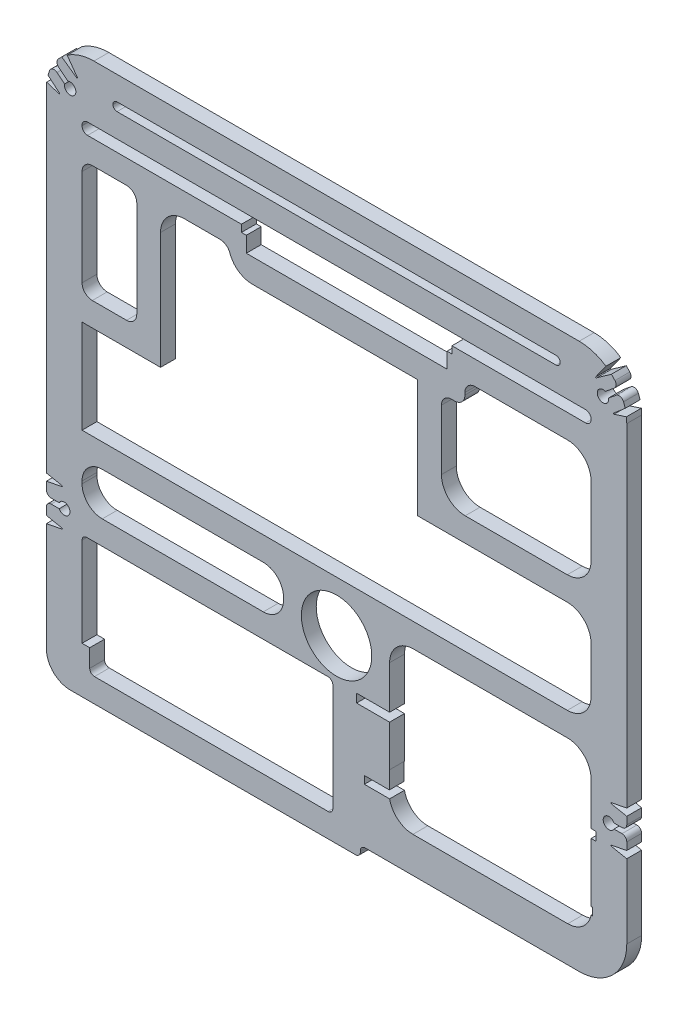
SolidWorks part; units mm, degrees
ref_plane "Front Plane" through (0, 0, 0) normal (0, 0, 1) x (1, 0, 0)
ref_plane "Top Plane" through (0, 0, 0) normal (0, 1, 0) x (1, 0, 0)
ref_plane "Right Plane" through (0, 0, 0) normal (1, 0, 0) x (0, 0, -1)
sketch "Sketch1" plane through (0, 0, 0) normal (0, 0, 1) x (1, 0, 0)
  line L0 (63.9883, 61.406) -> (63.9883, 57.596) construction
  line L1 (11.1776, 3.1158) -> (73.1542, 3.1158)
  line L2 (11.1776, 3.1158) -> (11.1776, 61.406)
  line L3 (11.1776, 61.406) -> (73.1542, 61.406)
  line L4 (73.1542, 3.1158) -> (73.1542, 61.406)
  line L5 (69.3442, 57.596) -> (14.9876, 57.596)
  line L6 (69.3442, 57.596) -> (69.3442, 6.9258)
  line L7 (69.3442, 6.9258) -> (14.9876, 6.9258)
  line L8 (14.9876, 57.596) -> (14.9876, 6.9258)
  line L9 (63.9883, 59.501) -> (18.0707, 59.501) construction
  line L10 (14.9876, 39.3805) -> (11.1776, 39.3805) construction
  line L11 (13.0826, 39.3805) -> (13.0826, 23.9527) construction
  line L12 (13.5248, 6.9258) -> (13.5248, 3.1158) construction
  line L13 (13.5248, 5.0208) -> (21.1598, 5.0208) construction
  line L14 (73.1542, 38.1916) -> (69.3442, 38.1916) construction
  line L15 (71.2492, 38.1916) -> (71.2492, 22.3321) construction
  line L16 (55.7422, 59.501) -> (30.5962, 59.501) construction
  line L19 (42.3087, 5.0208) -> (41.7626, 5.0208) construction
  line L21 (69.3442, 23.8281) -> (69.3442, 52.516) construction
  line L22 (14.9876, 47.563) -> (14.9876, 23.8281) construction
  dimension "D1" = 3.81
  dimension "D2" = 3.81
extrude "Boss-Extrude1" add sketch "Sketch1" along normal blind 1.5875
sketch "Sketch2" plane through (0, 0, 0) normal (0, 0, -1) x (-1, 0, 0)
  line L0 (-69.3442, 6.9258) -> (-69.3442, 57.596) construction
  line L1 (-69.3442, 26.6348) -> (-14.9876, 26.6348)
  line L2 (-69.3442, 26.6348) -> (-69.3442, 24.0948)
  line L3 (-69.3442, 24.0948) -> (-14.9876, 24.0948)
  line L4 (-14.9876, 26.6348) -> (-14.9876, 24.0948)
  line L5 (-14.9876, 57.596) -> (-14.9876, 6.9258) construction
  line L6 (-20.1206, 26.6348) -> (-57.8206, 26.6348) construction
  line L7 (-53.9642, 53.4304) -> (-53.9642, 51.7667)
  line L8 (-32.5266, 53.4304) -> (-32.0059, 53.4304)
  line L9 (-32.5266, 51.7667) -> (-53.9642, 51.7667) construction
  line L10 (-32.5266, 51.7667) -> (-32.5266, 53.4304) construction
  line L11 (-69.3442, 54.1924) -> (-54.4849, 54.1924)
  line L12 (-69.3442, 54.1924) -> (-69.3442, 51.6524)
  line L13 (-69.3442, 51.6524) -> (-55.8692, 51.6524)
  line L14 (-14.9876, 54.1924) -> (-14.9876, 51.6524)
  line L15 (-69.3442, 57.596) -> (-14.9876, 57.596)
  line L16 (-69.3442, 57.596) -> (-69.3442, 55.4243)
  line L17 (-69.3442, 55.4243) -> (-14.9876, 55.4243)
  line L18 (-14.9876, 57.596) -> (-14.9876, 55.4243)
  line L19 (-69.3442, 57.596) -> (-14.9876, 57.596) construction
  line L20 (-54.4849, 54.1924) -> (-54.4849, 53.4304)
  line L21 (-62.3462, 55.4243) -> (-23.9922, 55.4243) construction
  line L22 (-54.4849, 53.4304) -> (-53.9642, 53.4304)
  line L23 (-32.5266, 51.7667) -> (-53.9642, 51.7667)
  line L24 (-32.5266, 51.7667) -> (-32.5266, 53.4304)
  line L25 (-55.8692, 51.6524) -> (-55.8692, 49.2267)
  line L26 (-55.8692, 49.2267) -> (-30.6216, 49.2267)
  line L27 (-30.6216, 49.2267) -> (-30.6216, 51.6524)
  line L28 (-30.6216, 51.6524) -> (-14.9876, 51.6524)
  line L29 (-32.0059, 53.4304) -> (-32.0059, 54.1924)
  line L30 (-62.3462, 54.1924) -> (-23.9922, 54.1924) construction
  line L32 (-54.4849, 53.4304) -> (-54.4849, 54.1924) construction
  line L33 (-32.0059, 53.4304) -> (-54.4849, 53.4304) construction
  line L34 (-32.0059, 54.1924) -> (-14.9876, 54.1924)
  line L36 (-32.0059, 53.4304) -> (-32.0059, 54.1924) construction
  line L37 (-32.5266, 51.7667) -> (-32.5266, 53.4304) construction
  dimension "D1" = 2.54
  dimension "D2" = 1.905
  dimension "D3" = 2.54
  dimension "D4" = 1.905
  dimension "D5" = 2.54
extrude "Boss-Extrude2" add sketch "Sketch2" against normal up to surface (1.5875 mm away) up to face at (42.1659, 32.2609, 1.5875)
sketch "Sketch3" plane through (0, 0, 0) normal (0, 0, -1) x (-1, 0, 0)
  line L0 (-57.8206, 36.6348) -> (-50.8206, 36.6348) construction
  line L1 (-57.8206, 36.6348) -> (-50.8206, 36.6348)
  line L2 (-57.8206, 36.6348) -> (-69.3442, 36.6348)
  line L3 (-69.3442, 26.6348) -> (-69.3442, 51.6524) construction
  line L4 (-69.3442, 36.6348) -> (-69.3442, 39.1748)
  line L5 (-69.3442, 39.1748) -> (-53.3606, 39.1748)
  line L6 (-50.8206, 28.408) -> (-50.8206, 36.6348)
  line L7 (-50.8206, 28.408) -> (-50.8206, 49.2267)
  line L8 (-55.8692, 49.2267) -> (-30.6216, 49.2267) construction
  line L9 (-50.8206, 49.2267) -> (-53.3606, 49.2267)
  line L10 (-53.3606, 49.2267) -> (-53.3606, 39.1748)
  line L11 (-23.3706, 36.6348) -> (-20.1206, 36.6348) construction
  line L12 (-23.3706, 36.6348) -> (-20.1206, 36.6348)
  line L13 (-20.1206, 36.6348) -> (-14.9876, 36.6348)
  line L14 (-14.9876, 51.6524) -> (-14.9876, 26.6348) construction
  line L15 (-14.9876, 36.6348) -> (-14.9876, 39.1748)
  line L16 (-14.9876, 39.1748) -> (-20.8306, 39.1748)
  line L17 (-20.8306, 39.1748) -> (-20.8306, 51.6524)
  line L18 (-30.6216, 51.6524) -> (-14.9876, 51.6524) construction
  line L19 (-20.8306, 51.6524) -> (-23.3706, 51.6524)
  line L20 (-23.3706, 51.6524) -> (-23.3706, 36.6348)
  line L21 (-23.3706, 36.6348) -> (-16.2412, 25.8471)
  line M22 (-69.3442, 26.6348) -> (-69.3442, 51.6524)
  line M25 (-55.8692, 49.2267) -> (-30.6216, 49.2267)
  line M27 (-30.6216, 51.6524) -> (-14.9876, 51.6524)
  line M28 (-14.9876, 51.6524) -> (-14.9876, 26.6348)
  dimension "D1" = 2.54
  dimension "D2" = 2.54
  dimension "D3" = 2.54
  dimension "D4" = 2.54
extrude "Boss-Extrude3" add sketch "Sketch3" against normal up to surface (1.5875 mm away) contours L10 L5 L2 L1 L6 L7 M25 M22 | L20 L12 L13 L16 L17 M27 M28 region at (63.5824, 36.8588, 0) region at (20.9265, 42.3962, 0) up to face at (42.8855, 53.7395, 1.5875)
sketch "Sketch4" plane through (0, 0, 0) normal (0, 0, -1) x (-1, 0, 0)
  line L0 (-69.3442, 24.0948) -> (-14.9876, 24.0948) construction
  line L1 (-47.8301, 24.0948) -> (-36.5017, 24.0948)
  line L2 (-47.8301, 24.0948) -> (-47.8301, 6.9258)
  line L3 (-47.8301, 6.9258) -> (-36.5017, 6.9258)
  line L4 (-36.5017, 24.0948) -> (-36.5017, 6.9258)
  line L5 (-14.9876, 6.9258) -> (-69.3442, 6.9258) construction
  line L6 (-45.9251, 21.2246) -> (-47.8301, 21.2246) construction
  line L7 (-38.4067, 21.2246) -> (-36.5017, 21.2246) construction
  circle A0 centre (-42.1659, 21.2246) radius 3.7592 construction
  dimension "D1" = 1.905
extrude "Boss-Extrude4" add sketch "Sketch4" against normal up to surface (1.5875 mm away) up to face at (17.9091, 45.4136, 1.5875)
sketch "Sketch5" plane through (0, 0, 0) normal (0, 0, -1) x (-1, 0, 0)
  line L0 (-15.8038, 16.9715) -> (-41.7626, 16.9715) construction
  line L3 (-41.7626, 4.5128) -> (-41.7626, 16.9715) construction
  line L4 (-15.8038, 4.5128) -> (-41.7626, 4.5128) construction
  line L5 (-15.8038, 4.5128) -> (-15.8038, 16.9715) construction
  line L6 (-15.8038, 16.9715) -> (-41.7626, 16.9715)
  line L7 (-41.7626, 4.5128) -> (-41.7626, 16.9715)
  line L8 (-15.8038, 4.5128) -> (-41.7626, 4.5128)
  line L9 (-15.8038, 4.5128) -> (-15.8038, 16.9715)
  circle A0 centre (-42.1659, 21.2246) radius 3.7592 construction
  circle A1 centre (-42.1659, 21.2246) radius 3.7592
extrude "Cut-Extrude1" cut sketch "Sketch5" against normal up to surface (1.5875 mm away) up to face at (58.5871, 15.5103, 1.5875)
sketch "Sketch8" plane through (0, 0, 0) normal (0, 0, -1) x (-1, 0, 0)
  line L1 (-36.5017, 16.9715) -> (-14.9876, 16.9715)
  line L2 (-36.5017, 16.9715) -> (-36.5017, 19.5115)
  line L3 (-36.5017, 19.5115) -> (-14.9876, 19.5115)
  line L4 (-14.9876, 16.9715) -> (-14.9876, 19.5115)
  line L5 (-14.9876, 24.0948) -> (-14.9876, 6.9258) construction
  dimension "D1" = 2.54
extrude "Boss-Extrude5" add sketch "Sketch8" against normal up to surface (1.5875 mm away) up to face at (38.4067, 21.2246, 1.5875)
fillet "Fillet1" radius 5.08 3 edges at (73.1542, 3.1158, 0.7937) (11.1776, 61.406, 0.7937) (73.1542, 61.406, 0.7937)
fillet "Fillet2" radius 2.54 7 edges at (23.3706, 51.6524, 0.7937) (30.6216, 49.2267, 0.7937) (69.3442, 51.6524, 0.7937) (53.3606, 39.1748, 0.7937) (69.3442, 26.6348, 0.7937) (69.3442, 39.1748, 0.7937) (69.3442, 36.6348, 0.7937)
fillet "Fillet3" radius 1.0922 8 edges at (53.3606, 49.2267, 0.7937) (55.8692, 49.2267, 0.7937) (55.8692, 51.6524, 0.7937) (14.9876, 39.1748, 0.7937) (20.8306, 39.1748, 0.7937) (14.9876, 51.6524, 0.7937) (20.8306, 51.6524, 0.7937) (30.6216, 51.6524, 0.7937)
fillet "Fillet4" radius 0.5842 4 edges at (14.9876, 55.4243, 0.7937) (69.3442, 55.4243, 0.7937) (69.3442, 54.1924, 0.7937) (14.9876, 54.1924, 0.7937)
fillet "Fillet8" radius 2.159 4 edges at (36.5017, 19.5115, 0.7937) (36.5017, 24.0948, 0.7937) (14.9876, 24.0948, 0.7938) (14.9876, 19.5115, 0.7937)
sketch "Sketch6" plane through (0, 0, 0) normal (0, 0, -1) x (-1, 0, 0)
  line L0 (-16.6206, 28.1348) -> (-18.1206, 26.6348) construction
  line L1 (-18.1206, 36.6348) -> (-16.6206, 35.1348) construction
  line L2 (-16.6206, 35.1348) -> (-16.6206, 28.1348) construction
  line L3 (-16.6206, 28.1348) -> (-18.1206, 26.6348)
  line L4 (-18.1206, 36.6348) -> (-16.6206, 35.1348)
  line L5 (-16.6206, 35.1348) -> (-16.6206, 28.1348)
  line L6 (-18.1206, 36.6348) -> (-18.1206, 26.6348)
  circle A0 centre (-71.2492, 18.4306) radius 0.6096 construction
  circle A1 centre (-71.2492, 18.4306) radius 0.6096
  circle A4 centre (-70.6142, 57.596) radius 0.6096 construction
  circle A5 centre (-70.6142, 57.596) radius 0.6096
  circle A6 centre (-13.0826, 18.4306) radius 0.6096 construction
  circle A7 centre (-13.0826, 18.4306) radius 0.6096
  circle A10 centre (-13.7176, 57.596) radius 0.6096 construction
  circle A11 centre (-13.7176, 57.596) radius 0.6096
extrude "Cut-Extrude2" cut sketch "Sketch6" against normal up to surface (1.5875 mm away) up to face at (24.1846, 9.4701, 1.5875)
sketch "Sketch7" plane through (0, 0, 0) normal (0, 0, -1) x (-1, 0, 0)
  line L0 (-44.3026, 16.9715) -> (-69.8804, 16.9715) construction
  line L1 (-69.8804, 16.9715) -> (-69.8804, 16.0571) construction
  line L2 (-69.8804, 16.0571) -> (-44.3026, 16.0571) construction
  line L3 (-44.3026, 16.0571) -> (-44.3026, 16.9715) construction
  line L4 (-45.1366, 9.7751) -> (-69.5206, 9.7751) construction
  line L5 (-69.5206, 9.7751) -> (-69.5206, 8.9623) construction
  line L6 (-69.5206, 8.9623) -> (-45.1366, 8.9623) construction
  line L7 (-45.1366, 8.9623) -> (-45.1366, 9.7751) construction
  line L8 (-44.3026, 16.9715) -> (-69.8804, 16.9715)
  line L9 (-69.8804, 16.9715) -> (-69.8804, 16.0571)
  line L10 (-69.8804, 16.0571) -> (-44.3026, 16.0571)
  line L11 (-44.3026, 16.0571) -> (-44.3026, 16.9715)
  line L12 (-45.1366, 9.7751) -> (-69.5206, 9.7751)
  line L13 (-69.5206, 9.7751) -> (-69.5206, 8.9623)
  line L14 (-69.5206, 8.9623) -> (-45.1366, 8.9623)
  line L15 (-45.1366, 8.9623) -> (-45.1366, 9.7751)
  line L20 (-66.8536, 9.7751) -> (-47.8036, 9.7751)
  line L21 (-47.8036, 9.7751) -> (-47.8036, 11.6547)
  line L22 (-47.8036, 11.6547) -> (-66.8536, 11.6547)
  line L23 (-66.8536, 11.6547) -> (-66.8536, 9.7751)
  line L24 (-66.8536, 9.7751) -> (-47.8036, 9.7751)
  line L25 (-47.8036, 9.7751) -> (-47.8036, 11.6547)
  line L26 (-47.8036, 11.6547) -> (-66.8536, 11.6547)
  line L27 (-66.8536, 11.6547) -> (-66.8536, 9.7751)
  dimension "D1" = 0
extrude "Cut-Extrude3" cut sketch "Sketch7" against normal up to surface (1.5875 mm away) contours L14 L15 L12 L13 | L26 L27 L12 L25 | L10 L11 L8 L9 region at (57.0915, 16.5143, 0) region at (57.3286, 9.3687, 0) region at (57.3286, 10.7149, 0) up to face at (13.108, 57.596, 1.5875)
fillet "Fillet6" radius 0.508 4 edges at (41.7626, 16.9715, 0.7937) (41.7626, 4.5128, 0.7937) (15.8038, 4.5128, 0.7937) (14.9876, 16.9715, 0.7937)
sketch "Sketch9" plane through (0, 0, 1.5875) normal (0, 0, 1) x (1, 0, 0)
  line L0 (68.0742, 61.406) -> (16.2576, 61.406) construction
  line L1 (18.2896, 58.866) -> (66.0422, 58.866)
  line L2 (18.2896, 58.866) -> (18.2896, 57.9643)
  line L3 (18.2896, 57.9643) -> (66.0422, 57.9643)
  line L8 (66.0422, 58.866) -> (66.0422, 57.9643)
  line L9 (15.5718, 55.4243) -> (68.76, 55.4243) construction
  line L10 (11.1776, 56.326) -> (11.1776, 59.3208) construction
  line L11 (18.2896, 58.866) -> (11.1776, 58.866) construction
  line L13 (66.0422, 58.866) -> (73.1542, 58.866) construction
  line L14 (73.1542, 56.326) -> (73.1542, 56.8419) construction
  dimension "D1" = 2.54
  dimension "D2" = 2.54
  dimension "D3" = 7.112
extrude "Cut-Extrude4" cut sketch "Sketch9" against normal up to surface (1.5875 mm away) up to face at (57.106, 13.2916, 0)
fillet "Fillet7" radius 0.4318 4 edges at (18.2896, 57.9643, 0.7937) (18.2896, 58.866, 0.7937) (66.0422, 57.9643, 0.7937) (66.0422, 58.866, 0.7937)
fillet "Fillet9" radius 2.54 4 edges at (69.3442, 6.9258, 0.7937) (47.8301, 6.9258, 0.7937) (69.3442, 24.0948, 0.7937) (47.8301, 24.0948, 0.7937)
sketch "Sketch10" plane through (0, 0, 1.5875) normal (0, 0, 1) x (1, 0, 0)
  line L0 (42.1659, 24.9838) -> (42.1659, -13.4858) construction
  line L1 (11.1776, 3.1158) -> (44.7059, 3.1158)
  line L2 (11.1776, 3.1158) -> (11.1776, 1.9728)
  line L3 (11.1776, 1.9728) -> (44.7059, 1.9728)
  line L4 (44.7059, 3.1158) -> (44.7059, 1.9728)
  line L5 (16.3118, 4.5128) -> (41.2546, 4.5128) construction
  circle A0 centre (42.1659, 21.2246) radius 3.7592 construction
  dimension "D1" = 2.54
  dimension "D2" = 2.54
extrude "Boss-Extrude6" add sketch "Sketch10" against normal up to surface (1.5875 mm away) up to face at (42.1659, 58.4152, 0)
fillet "Fillet10" radius 2.54 1 edges at (11.1776, 1.9728, 0.7937)
fillet "Fillet11" radius 0.508 2 edges at (44.7059, 3.1158, 0.7937) (44.7059, 1.9728, 0.7937)
sketch "Sketch11" plane through (0, 0, 1.5875) normal (0, 0, 1) x (1, 0, 0)
  line L0 (14.486, 59.0031) -> (13.3987, 60.5253) construction
  line L1 (12.8232, 60.0693) -> (14.4151, 58.9322) construction
  line L2 (13.4744, 58.155) -> (12.501, 58.9492) construction
  line L3 (12.3178, 58.3774) -> (13.1211, 57.7221) construction
  line L4 (12.5786, 56.6017) -> (11.3522, 57.6466) construction
  line L5 (11.2145, 56.9374) -> (12.5302, 56.5147) construction
  line L6 (69.8457, 59.0031) -> (70.933, 60.5253) construction
  line L7 (71.5085, 60.0693) -> (69.9166, 58.9322) construction
  line L8 (70.8574, 58.155) -> (71.8308, 58.9492) construction
  line L9 (72.0139, 58.3774) -> (71.2106, 57.7221) construction
  line L10 (71.7531, 56.6017) -> (72.9795, 57.6466) construction
  line L11 (73.1172, 56.9374) -> (71.8016, 56.5147) construction
  line L12 (71.4982, 20.4444) -> (73.1542, 20.7756) construction
  line L13 (73.1542, 20.0136) -> (71.4982, 20.3448) construction
  line L14 (71.791, 18.71) -> (72.6462, 18.71) construction
  line L15 (72.6462, 18.1512) -> (71.791, 18.1512) construction
  line L16 (71.4982, 16.5165) -> (73.1542, 16.8477) construction
  line L17 (73.1542, 16.0857) -> (71.4982, 16.4169) construction
  line L18 (14.486, 59.0031) -> (13.3987, 60.5253)
  line L19 (12.8232, 60.0693) -> (14.4151, 58.9322)
  line L20 (13.4744, 58.155) -> (12.501, 58.9492)
  line L21 (12.3178, 58.3774) -> (13.1211, 57.7221)
  line L22 (12.5786, 56.6017) -> (11.3522, 57.6466)
  line L23 (11.2145, 56.9374) -> (12.5302, 56.5147)
  line L24 (69.8457, 59.0031) -> (70.933, 60.5253)
  line L25 (71.5085, 60.0693) -> (69.9166, 58.9322)
  line L26 (70.8574, 58.155) -> (71.8308, 58.9492)
  line L27 (72.0139, 58.3774) -> (71.2106, 57.7221)
  line L28 (71.7531, 56.6017) -> (72.9795, 57.6466)
  line L29 (73.1172, 56.9374) -> (71.8016, 56.5147)
  line L30 (71.4982, 20.4444) -> (73.1542, 20.7756)
  line L31 (73.1542, 20.0136) -> (71.4982, 20.3448)
  line L32 (71.791, 18.71) -> (72.6462, 18.71)
  line L33 (72.6462, 18.1512) -> (71.791, 18.1512)
  line L34 (71.4982, 16.5165) -> (73.1542, 16.8477)
  line L35 (73.1542, 16.0857) -> (71.4982, 16.4169)
  line L36 (12.8335, 20.4444) -> (11.1776, 20.7756) construction
  line L37 (11.1776, 20.0136) -> (12.8335, 20.3448) construction
  line L38 (12.5408, 18.71) -> (11.6856, 18.71) construction
  line L39 (11.6856, 18.1512) -> (12.5408, 18.1512) construction
  line L40 (12.8335, 16.5165) -> (11.1776, 16.8477) construction
  line L41 (11.1776, 16.0857) -> (12.8335, 16.4169) construction
  line L42 (12.8335, 20.4444) -> (11.1776, 20.7756)
  line L43 (11.1776, 20.0136) -> (12.8335, 20.3448)
  line L44 (12.5408, 18.71) -> (11.6856, 18.71)
  line L45 (11.6856, 18.1512) -> (12.5408, 18.1512)
  line L46 (12.8335, 16.5165) -> (11.1776, 16.8477)
  line L47 (11.1776, 16.0857) -> (12.8335, 16.4169)
  line L48 (11.1776, 56.326) -> (11.1776, 4.5128) construction
  line L49 (73.1542, 8.1958) -> (73.1542, 56.326) construction
  line L50 (11.1776, 20.7756) -> (11.1776, 20.0136)
  line L51 (73.1542, 16.0857) -> (73.1542, 16.8477)
  line L52 (73.1542, 17.6432) -> (73.1542, 19.218)
  line L53 (73.1542, 20.0136) -> (73.1542, 20.7756)
  line L54 (11.1776, 19.218) -> (11.1776, 17.6432)
  line L55 (11.1776, 16.8477) -> (11.1776, 16.0857)
  arc A0 (14.4151, 58.9322) -> (14.486, 59.0031) centre (14.4446, 58.9736) ccw construction
  arc A1 (12.4404, 59.678) -> (12.501, 58.9492) centre (12.8221, 59.3428) ccw construction
  arc A2 (12.3178, 58.3774) -> (11.5233, 58.168) centre (11.9967, 57.9838) ccw construction
  arc A3 (12.5302, 56.5147) -> (12.5786, 56.6017) centre (12.5457, 56.5631) ccw construction
  arc A4 (69.8457, 59.0031) -> (69.9166, 58.9322) centre (69.8871, 58.9736) ccw construction
  arc A5 (71.8308, 58.9492) -> (71.8913, 59.678) centre (71.5096, 59.3428) ccw construction
  arc A6 (72.8085, 58.168) -> (72.0139, 58.3774) centre (72.335, 57.9838) ccw construction
  arc A7 (71.7531, 56.6017) -> (71.8016, 56.5147) centre (71.786, 56.5631) ccw construction
  arc A8 (71.4982, 20.4444) -> (71.4982, 20.3448) centre (71.5082, 20.3946) ccw construction
  arc A9 (72.6462, 18.71) -> (73.1542, 19.218) centre (72.6462, 19.218) ccw construction
  arc A10 (73.1542, 17.6432) -> (72.6462, 18.1512) centre (72.6462, 17.6432) ccw construction
  arc A11 (71.4982, 16.5165) -> (71.4982, 16.4169) centre (71.5082, 16.4667) ccw construction
  arc A12 (14.4151, 58.9322) -> (14.486, 59.0031) centre (14.4446, 58.9736) ccw
  arc A13 (12.4404, 59.678) -> (12.501, 58.9492) centre (12.8221, 59.3428) ccw
  arc A14 (12.3178, 58.3774) -> (11.5233, 58.168) centre (11.9967, 57.9838) ccw
  arc A15 (12.5302, 56.5147) -> (12.5786, 56.6017) centre (12.5457, 56.5631) ccw
  arc A16 (69.8457, 59.0031) -> (69.9166, 58.9322) centre (69.8871, 58.9736) ccw
  arc A17 (71.8308, 58.9492) -> (71.8913, 59.678) centre (71.5096, 59.3428) ccw
  arc A18 (72.8085, 58.168) -> (72.0139, 58.3774) centre (72.335, 57.9838) ccw
  arc A19 (71.7531, 56.6017) -> (71.8016, 56.5147) centre (71.786, 56.5631) ccw
  arc A20 (71.4982, 20.4444) -> (71.4982, 20.3448) centre (71.5082, 20.3946) ccw
  arc A21 (72.6462, 18.71) -> (73.1542, 19.218) centre (72.6462, 19.218) ccw
  arc A22 (73.1542, 17.6432) -> (72.6462, 18.1512) centre (72.6462, 17.6432) ccw
  arc A23 (71.4982, 16.5165) -> (71.4982, 16.4169) centre (71.5082, 16.4667) ccw
  arc A24 (12.8335, 20.3448) -> (12.8335, 20.4444) centre (12.8235, 20.3946) ccw construction
  arc A25 (11.1776, 19.218) -> (11.6856, 18.71) centre (11.6856, 19.218) ccw construction
  arc A26 (11.6856, 18.1512) -> (11.1776, 17.6432) centre (11.6856, 17.6432) ccw construction
  arc A27 (12.8335, 16.4169) -> (12.8335, 16.5165) centre (12.8235, 16.4667) ccw construction
  arc A28 (12.8335, 20.3448) -> (12.8335, 20.4444) centre (12.8235, 20.3946) ccw
  arc A29 (11.1776, 19.218) -> (11.6856, 18.71) centre (11.6856, 19.218) ccw
  arc A30 (11.6856, 18.1512) -> (11.1776, 17.6432) centre (11.6856, 17.6432) ccw
  arc A31 (12.8335, 16.4169) -> (12.8335, 16.5165) centre (12.8235, 16.4667) ccw
  circle A32 centre (13.0826, 18.4306) radius 0.6096 construction
  arc A33 (16.2576, 61.406) -> (11.1776, 56.326) centre (16.2576, 56.326) ccw construction
  circle A34 centre (13.7176, 57.596) radius 0.6096 construction
  arc A35 (73.1542, 56.326) -> (68.0742, 61.406) centre (68.0742, 56.326) ccw construction
  circle A36 centre (70.6142, 57.596) radius 0.6096 construction
  circle A37 centre (71.2492, 18.4306) radius 0.6096 construction
  arc A38 (12.5408, 18.71) -> (12.5408, 18.1512) centre (13.0826, 18.4306) ccw
  arc A39 (13.3987, 60.5253) -> (12.8232, 60.0693) centre (16.2576, 56.326) ccw
  arc A40 (13.4744, 58.155) -> (13.1211, 57.7221) centre (13.7176, 57.596) ccw
  arc A41 (73.1172, 56.9374) -> (72.9795, 57.6466) centre (68.0742, 56.326) ccw
  arc A42 (71.2106, 57.7221) -> (70.8574, 58.155) centre (70.6142, 57.596) ccw
  arc A43 (71.791, 18.1512) -> (71.791, 18.71) centre (71.2492, 18.4306) ccw
  arc A44 (72.8085, 58.168) -> (71.8913, 59.678) centre (68.0742, 56.326) ccw
  arc A45 (71.5085, 60.0693) -> (70.933, 60.5253) centre (68.0742, 56.326) ccw
  arc A46 (12.4404, 59.678) -> (11.5233, 58.168) centre (16.2576, 56.326) ccw
  arc A47 (11.3522, 57.6466) -> (11.2145, 56.9374) centre (16.2576, 56.326) ccw
extrude "Cut-Extrude5" cut sketch "Sketch11" against normal through all
